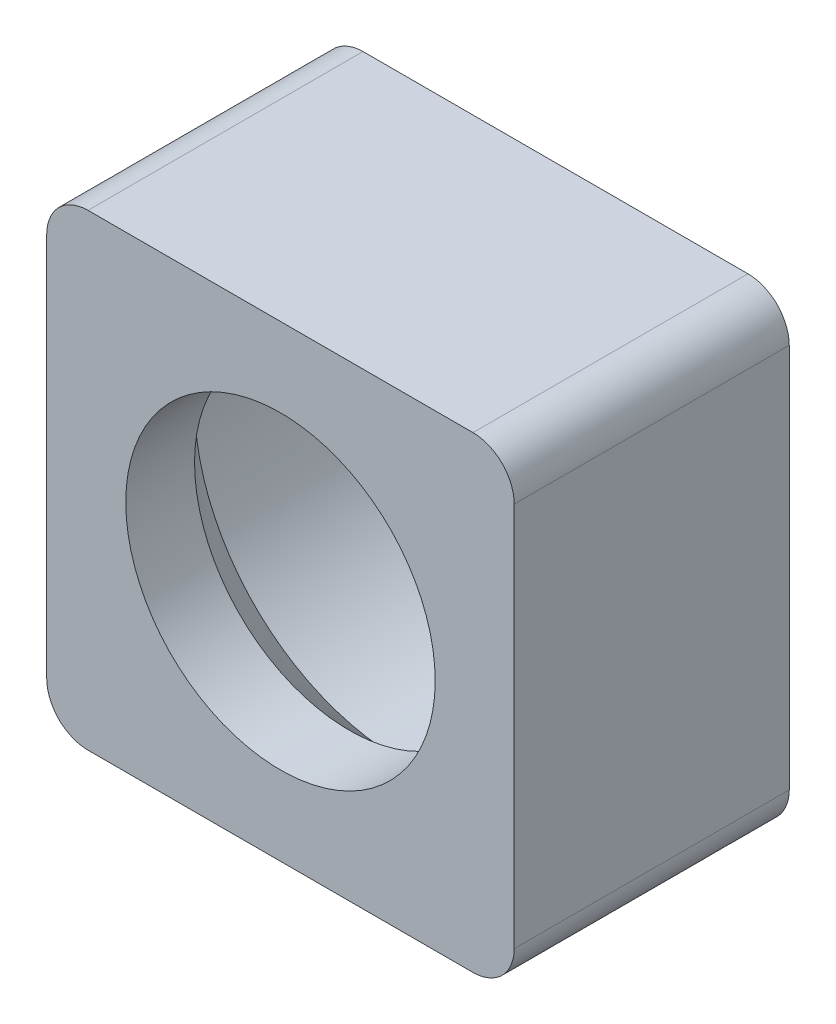
SolidWorks part; units mm, degrees
ref_plane "Front" through (0, 0, 0) normal (0, 0, 1) x (1, 0, 0)
ref_plane "Top" through (0, 0, 0) normal (0, 1, 0) x (1, 0, 0)
ref_plane "Right" through (0, 0, 0) normal (1, 0, 0) x (0, 0, -1)
sketch "Sketch1" plane through (0, 0, 0) normal (0, 0, 1) x (1, 0, 0)
  line L0 (-3.3999, 2.8) -> (-3.3999, -2.8)
  line L1 (-2.7999, -3.4) -> (2.7999, -3.4)
  line L2 (3.3999, -2.8) -> (3.3999, 2.8)
  line L3 (2.7999, 3.4) -> (-2.7999, 3.4)
  spline S0 degree 3 poles (-3.3999, -2.8) (-3.3999, -2.9531) (-3.2719, -3.272) (-2.953, -3.4) (-2.7999, -3.4) knots -1.570796 -1.570796 -1.570796 -1.570796 -0.785398 0 0 0 0
  spline S1 degree 3 poles (2.7999, -3.4) (2.953, -3.4) (3.2719, -3.272) (3.3999, -2.9531) (3.3999, -2.8) knots 0 0 0 0 0.785398 1.570796 1.570796 1.570796 1.570796
  spline S2 degree 3 poles (3.3999, 2.8) (3.3999, 2.9531) (3.2719, 3.272) (2.953, 3.4) (2.7999, 3.4) knots 1.570796 1.570796 1.570796 1.570796 2.356194 3.141593 3.141593 3.141593 3.141593
  spline S3 degree 3 poles (-2.7999, 3.4) (-2.953, 3.4) (-3.2719, 3.272) (-3.3999, 2.9531) (-3.3999, 2.8) knots -3.141593 -3.141593 -3.141593 -3.141593 -2.356194 -1.570796 -1.570796 -1.570796 -1.570796
extrude "Boss-Extrude1" add sketch "Sketch1" along normal blind 4
sketch "Sketch2" plane through (0, 0, 4) normal (0, 0, 1) x (1, 0, 0)
  line L0 (0, 3.4) -> (0, -3.4) construction
  line L1 (2.7999, 3.4) -> (-2.7999, 3.4) construction
  line L2 (-2.7999, -3.4) -> (2.7999, -3.4) construction
  line L3 (-3.3999, 0) -> (3.3999, 0) construction
  line L4 (-3.3999, 2.8) -> (-3.3999, -2.8) construction
  line L5 (3.3999, -2.8) -> (3.3999, 2.8) construction
  circle A0 centre (0, 0) radius 2.25
  dimension "D1" = 4.5
extrude "Cut-Extrude1" cut sketch "Sketch2" against normal up to surface (4 mm away) up to face at (0, 0, 0)
sketch "Sketch3" plane through (0, 0, 0) normal (0, 0, -1) x (-1, 0, 0)
  line L0 (0, 3.4) -> (0, -3.4) construction
  line L1 (-2.7999, 3.4) -> (2.7999, 3.4) construction
  line L2 (2.7999, -3.4) -> (-2.7999, -3.4) construction
  line L3 (-3.3999, 0) -> (3.3999, 0) construction
  line L4 (-3.3999, -2.8) -> (-3.3999, 2.8) construction
  line L5 (3.3999, 2.8) -> (3.3999, -2.8) construction
  circle A0 centre (0, 0) radius 3
extrude "Cut-Extrude2" cut sketch "Sketch3" against normal blind 2
chamfer "Chamfer1" distance 1 angle 45 1 edges at (-2.25, 0, 2)
